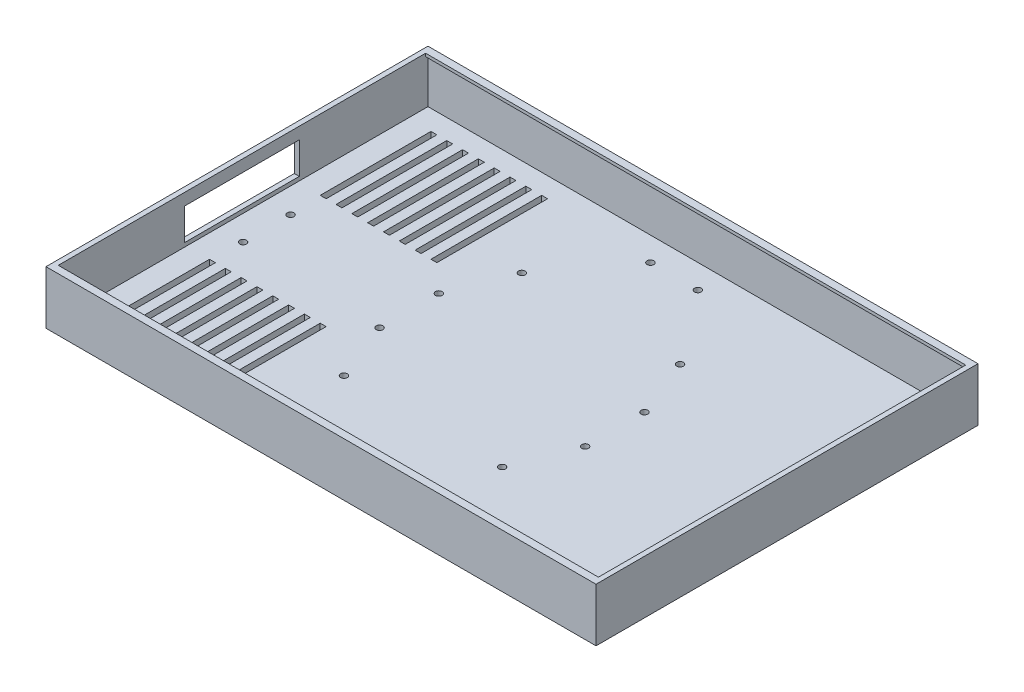
SolidWorks part; units mm, degrees
ref_plane "Front Plane" through (0, 0, 0) normal (0, 0, 1) x (1, 0, 0)
ref_plane "Top Plane" through (0, 0, 0) normal (0, 1, 0) x (1, 0, 0)
ref_plane "Right Plane" through (0, 0, 0) normal (1, 0, 0) x (0, 0, -1)
sketch "Sketch1" plane through (0, 0, 0) normal (0, 1, 0) x (1, 0, 0)
  line L1 (-139.1, -96.6) -> (139.1, -96.6)
  line L2 (-139.1, -96.6) -> (-139.1, 96.6)
  line L3 (-139.1, 96.6) -> (139.1, 96.6)
  line L4 (139.1, -96.6) -> (139.1, 96.6)
  line L5 (-139.1, -96.6) -> (139.1, 96.6) construction
  line L6 (-139.1, 96.6) -> (139.1, -96.6) construction
  dimension "D1" = 278.2
  dimension "D2" = 193.2
extrude "Shell Block" add sketch "Sketch1" along normal blind 27
ref_plane "Shell Front" through (0, 27, 0) normal (0, 1, 0) x (1, 0, 0)
sketch "Sketch2" plane through (0, 27, 0) normal (0, 1, 0) x (1, 0, 0)
  line L1 (-136.6, -92.9) -> (136.6, -92.9)
  line L2 (-136.6, -92.9) -> (-136.6, 92.9)
  line L3 (-136.6, 92.9) -> (136.6, 92.9)
  line L4 (136.6, -92.9) -> (136.6, 92.9)
  line L5 (-136.6, -92.9) -> (136.6, 92.9) construction
  line L6 (-136.6, 92.9) -> (136.6, -92.9) construction
  dimension "D1" = 273.2
  dimension "D2" = 185.8
extrude "Front Opening" cut sketch "Sketch2" against normal blind 1.5
ref_plane "Under Lip" through (0, 25.5, 0) normal (0, 1, 0) x (1, 0, 0)
sketch "Sketch3" plane through (0, 25.5, 0) normal (0, 1, 0) x (1, 0, 0)
  line L1 (-136.6, -94.1) -> (136.6, -94.1)
  line L2 (-136.6, -94.1) -> (-136.6, 94.1)
  line L3 (-136.6, 94.1) -> (136.6, 94.1)
  line L4 (136.6, -94.1) -> (136.6, 94.1)
  line L5 (-136.6, -94.1) -> (136.6, 94.1) construction
  line L6 (-136.6, 94.1) -> (136.6, -94.1) construction
  dimension "D1" = 273.2
  dimension "D2" = 188.2
extrude "Display Pocket" cut sketch "Sketch3" against normal blind 22.5
ref_plane "Back Inner" through (0, 3, 0) normal (0, 1, 0) x (1, 0, 0)
sketch "Sketch4" plane through (0, 3, 0) normal (0, 1, 0) x (1, 0, 0)
  line L1 (-69, 28) -> (-66, 28)
  line L2 (-69, 28) -> (-69, 84)
  line L3 (-69, 84) -> (-66, 84)
  line L4 (-66, 28) -> (-66, 84)
  line L6 (-69, -84) -> (-66, -84)
  line L7 (-69, -84) -> (-69, -28)
  line L8 (-69, -28) -> (-66, -28)
  line L9 (-66, -84) -> (-66, -28)
  line L11 (-77, 28) -> (-74, 28)
  line L12 (-77, 28) -> (-77, 84)
  line L13 (-77, 84) -> (-74, 84)
  line L14 (-74, 28) -> (-74, 84)
  line L16 (-77, -84) -> (-74, -84)
  line L17 (-77, -84) -> (-77, -28)
  line L18 (-77, -28) -> (-74, -28)
  line L19 (-74, -84) -> (-74, -28)
  line L21 (-85, 28) -> (-82, 28)
  line L22 (-85, 28) -> (-85, 84)
  line L23 (-85, 84) -> (-82, 84)
  line L24 (-82, 28) -> (-82, 84)
  line L26 (-85, -84) -> (-82, -84)
  line L27 (-85, -84) -> (-85, -28)
  line L28 (-85, -28) -> (-82, -28)
  line L29 (-82, -84) -> (-82, -28)
  line L31 (-93, 28) -> (-90, 28)
  line L32 (-93, 28) -> (-93, 84)
  line L33 (-93, 84) -> (-90, 84)
  line L34 (-90, 28) -> (-90, 84)
  line L36 (-93, -84) -> (-90, -84)
  line L37 (-93, -84) -> (-93, -28)
  line L38 (-93, -28) -> (-90, -28)
  line L39 (-90, -84) -> (-90, -28)
  line L41 (-101, 28) -> (-98, 28)
  line L42 (-101, 28) -> (-101, 84)
  line L43 (-101, 84) -> (-98, 84)
  line L44 (-98, 28) -> (-98, 84)
  line L46 (-101, -84) -> (-98, -84)
  line L47 (-101, -84) -> (-101, -28)
  line L48 (-101, -28) -> (-98, -28)
  line L49 (-98, -84) -> (-98, -28)
  line L51 (-109, 28) -> (-106, 28)
  line L52 (-109, 28) -> (-109, 84)
  line L53 (-109, 84) -> (-106, 84)
  line L54 (-106, 28) -> (-106, 84)
  line L56 (-109, -84) -> (-106, -84)
  line L57 (-109, -84) -> (-109, -28)
  line L58 (-109, -28) -> (-106, -28)
  line L59 (-106, -84) -> (-106, -28)
  line L61 (-117, 28) -> (-114, 28)
  line L62 (-117, 28) -> (-117, 84)
  line L63 (-117, 84) -> (-114, 84)
  line L64 (-114, 28) -> (-114, 84)
  line L66 (-117, -84) -> (-114, -84)
  line L67 (-117, -84) -> (-117, -28)
  line L68 (-117, -28) -> (-114, -28)
  line L69 (-114, -84) -> (-114, -28)
  line L71 (-125, 28) -> (-122, 28)
  line L72 (-125, 28) -> (-125, 84)
  line L73 (-125, 84) -> (-122, 84)
  line L74 (-122, 28) -> (-122, 84)
  line L76 (-125, -84) -> (-122, -84)
  line L77 (-125, -84) -> (-125, -28)
  line L78 (-125, -28) -> (-122, -28)
  line L79 (-122, -84) -> (-122, -28)
extrude "Vent Slots" cut sketch "Sketch4" against normal blind 4
sketch "Sketch5" plane through (0, 0, 0) normal (1, 0, 0) x (0, 0, -1)
  line L1 (-29, 5) -> (29, 5)
  line L2 (-29, 5) -> (-29, 21)
  line L3 (-29, 21) -> (29, 21)
  line L4 (29, 5) -> (29, 21)
extrude "Cable Exit (-X short side)" cut sketch "Sketch5" against normal blind 140.1
sketch "Sketch6" plane through (0, 3, 0) normal (0, 1, 0) x (1, 0, 0)
  circle A0 centre (-40, -45) radius 1.7
  circle A1 centre (-40, 45) radius 1.7
  circle A2 centre (40, -45) radius 1.7
  circle A3 centre (40, 45) radius 1.7
  circle A4 centre (-52, -15) radius 1.7
  circle A5 centre (-52, 15) radius 1.7
  circle A6 centre (52, -15) radius 1.7
  circle A7 centre (52, 15) radius 1.7
  circle A8 centre (-12, -82) radius 1.7
  circle A9 centre (-12, 82) radius 1.7
  circle A10 centre (12, -82) radius 1.7
  circle A11 centre (12, 82) radius 1.7
  circle A12 centre (-124, -12) radius 1.7
  circle A13 centre (-124, 12) radius 1.7
  circle A14 centre (124, -12) radius 1.7
  circle A15 centre (124, 12) radius 1.7
extrude "Bolt Holes" cut sketch "Sketch6" against normal blind 4
equation "\"DispL\" = 272.0"
equation "\"DispW\" = 187.0"
equation "\"DispT\" = 20.0"
equation "\"Clr\" = 0.6"
equation "\"Wall\" = 2.5"
equation "\"BackT\" = 3.0"
equation "\"CableRoom\" = 4.0"
equation "\"LipW\" = 1.2"
equation "\"LipT\" = 1.5"
equation "\"CableW\" = 58.0"
equation "\"CableH\" = 16.0"
equation "\"BoltD\" = 3.4"
equation "\"ShellL\" = \"DispL\" + 2 * \"Clr\" + 2 * \"Wall\""
equation "\"ShellW\" = \"DispW\" + 2 * \"Clr\" + 2 * \"Wall\""
equation "\"ShellH\" = \"BackT\" + \"DispT\" + \"CableRoom\""
equation "\"D1@Sketch1\" = \"ShellL\""
equation "\"D2@Sketch1\" = \"ShellW\""
equation "\"D1@Shell Block\" = \"ShellH\""
equation "\"D1@Shell Front\" = \"ShellH\""
equation "\"D1@Sketch2\" = \"DispL\" + 2 * \"Clr\""
equation "\"D2@Sketch2\" = \"DispW\" + 2 * \"Clr\" - 2 * \"LipW\""
equation "\"D1@Front Opening\" = \"LipT\""
equation "\"D1@Under Lip\" = \"ShellH\" - \"LipT\""
equation "\"D1@Sketch3\" = \"DispL\" + 2 * \"Clr\""
equation "\"D2@Sketch3\" = \"DispW\" + 2 * \"Clr\""
equation "\"D1@Display Pocket\" = \"ShellH\" - \"LipT\" - \"BackT\""
equation "\"D1@Back Inner\" = \"BackT\""
